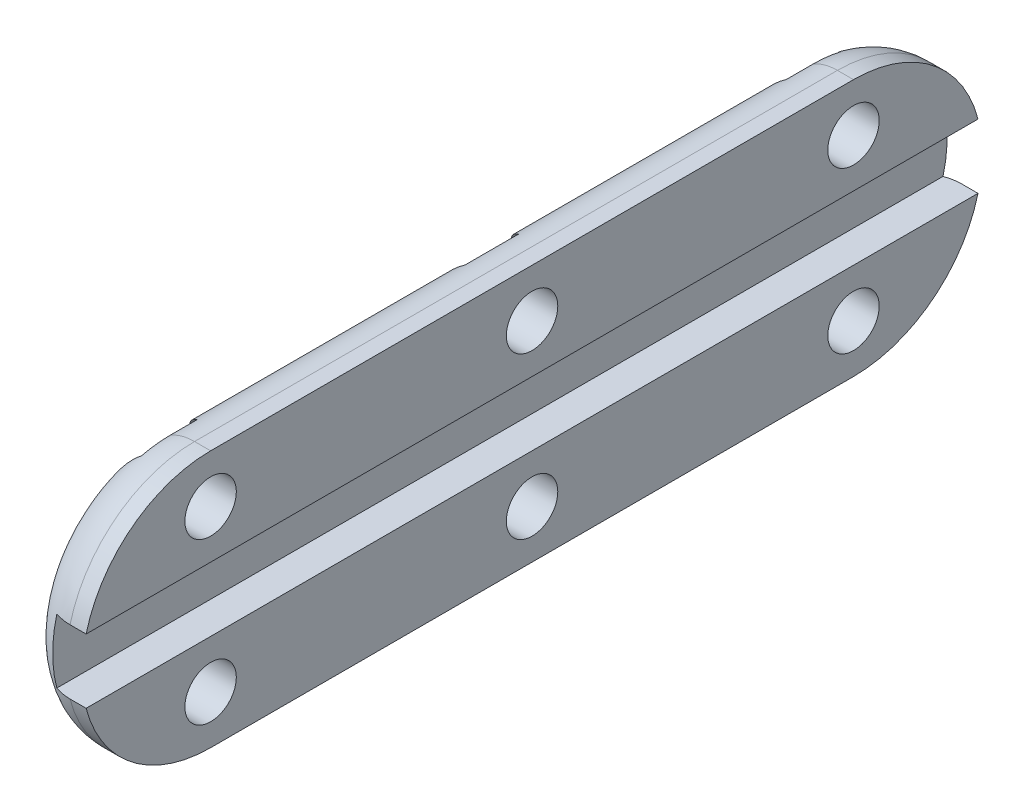
SolidWorks part; units mm, degrees
ref_plane "Front Plane" through (0, 0, 0) normal (0, 0, 1) x (1, 0, 0)
ref_plane "Top Plane" through (0, 0, 0) normal (0, 1, 0) x (1, 0, 0)
ref_plane "Right Plane" through (0, 0, 0) normal (1, 0, 0) x (0, 0, -1)
sketch "Sketch1" plane through (0, 0, 0) normal (1, 0, 0) x (0, 0, -1)
  line L0 (0, 8) -> (0, -8) construction
  line L1 (0, -8) -> (40, -8)
  line L2 (40, -8) -> (40, 8) construction
  line L3 (40, 8) -> (0, 8)
  arc A0 (0, 8) -> (0, -8) centre (0, 0) ccw
  arc A1 (40, 8) -> (40, -8) centre (40, 0) cw
  point P3 (0, 0)
  dimension "D1" = 16
  dimension "D2" = 40
extrude "Boss-Extrude1" add sketch "Sketch1" against normal blind 4
sketch "Sketch2" plane through (0, 0, 0) normal (0, 0, 1) x (1, 0, 0)
  line L0 (0, -8) -> (0, 8) construction
  line L1 (0, 2) -> (-2, 2)
  line L2 (0, 2) -> (0, -2)
  line L3 (0, -2) -> (-2, -2)
  line L4 (-2, 2) -> (-2, -2)
  point P6 (0, 0)
  dimension "D1" = 4
  dimension "D2" = 2
extrude "Cut-Extrude1" cut sketch "Sketch2" against normal through all both and the other way through all
sketch "Sketch3" plane through (0, 0, 0) normal (1, 0, 0) x (0, 0, -1)
  line L0 (0, 5) -> (40, 5) construction
  line L1 (0, 8) -> (0, -8) construction
  line L2 (40, -8) -> (40, 8) construction
  line L3 (0, -5) -> (40, -5) construction
  line L4 (40, 8) -> (0, 8) construction
  line L6 (0, -8) -> (40, -8) construction
  circle A0 centre (0, 5) radius 1.6
  circle A1 centre (40, 5) radius 1.6
  circle A2 centre (40, -5) radius 1.6
  circle A3 centre (0, -5) radius 1.6
  circle A4 centre (20, 5) radius 1.6
  circle A5 centre (20, -5) radius 1.6
  dimension "D3" = 3.2
  dimension "D1" = 3
  dimension "D2" = 3
extrude "Cut-Extrude2" cut sketch "Sketch3" against normal up to next
fillet "Fillet1" radius 3 4 edges at (-4, -8, -20) (-4, 0, 8) (-4, 8, -20) (-4, 0, -48)
sketch "Sketch4" plane through (-4, 0, 0) normal (-1, 0, 0) x (0, 0, 1)
  line L0 (0, 8) -> (0, -8) construction
  line L1 (-36.8246, 5) -> (-38.4123, 7.75)
  line L2 (-38.4123, 7.75) -> (-41.5877, 7.75)
  line L3 (-41.5877, 7.75) -> (-43.1754, 5)
  line L4 (-43.1754, 5) -> (-41.5877, 2.25)
  line L5 (-41.5877, 2.25) -> (-38.4123, 2.25)
  line L6 (-38.4123, 2.25) -> (-36.8246, 5)
  line L7 (-3.1754, 5) -> (-1.5877, 2.25)
  line L8 (-1.5877, 2.25) -> (1.5877, 2.25)
  line L9 (1.5877, 2.25) -> (3.1754, 5)
  line L10 (3.1754, 5) -> (1.5877, 7.75)
  line L11 (1.5877, 7.75) -> (-1.5877, 7.75)
  line L12 (-1.5877, 7.75) -> (-3.1754, 5)
  line L13 (0, 5) -> (-40, 5) construction
  line L14 (-3.1754, -5) -> (-1.5877, -7.75)
  line L15 (-1.5877, -7.75) -> (1.5877, -7.75)
  line L16 (1.5877, -7.75) -> (3.1754, -5)
  line L17 (3.1754, -5) -> (1.5877, -2.25)
  line L18 (1.5877, -2.25) -> (-1.5877, -2.25)
  line L19 (-1.5877, -2.25) -> (-3.1754, -5)
  line L20 (-36.8246, -5) -> (-38.4123, -2.25)
  line L21 (-38.4123, -2.25) -> (-41.5877, -2.25)
  line L22 (-41.5877, -2.25) -> (-43.1754, -5)
  line L23 (-43.1754, -5) -> (-41.5877, -7.75)
  line L24 (-41.5877, -7.75) -> (-38.4123, -7.75)
  line L25 (-38.4123, -7.75) -> (-36.8246, -5)
  line L26 (0, -5) -> (-40, -5) construction
  line L28 (-16.8246, 5) -> (-18.4123, 7.75)
  line L29 (-18.4123, 7.75) -> (-21.5877, 7.75)
  line L30 (-21.5877, 7.75) -> (-23.1754, 5)
  line L31 (-23.1754, 5) -> (-21.5877, 2.25)
  line L32 (-21.5877, 2.25) -> (-18.4123, 2.25)
  line L33 (-18.4123, 2.25) -> (-16.8246, 5)
  line L34 (-16.8246, -5) -> (-18.4123, -2.25)
  line L35 (-18.4123, -2.25) -> (-21.5877, -2.25)
  line L36 (-21.5877, -2.25) -> (-23.1754, -5)
  line L37 (-23.1754, -5) -> (-21.5877, -7.75)
  line L38 (-21.5877, -7.75) -> (-18.4123, -7.75)
  line L39 (-18.4123, -7.75) -> (-16.8246, -5)
  circle A0 centre (-40, 5) radius 2.75 construction
  circle A1 centre (0, 5) radius 2.75 construction
  circle A2 centre (0, -5) radius 2.75 construction
  circle A3 centre (-40, -5) radius 2.75 construction
  circle A4 centre (-20, 5) radius 2.75 construction
  circle A5 centre (-20, -5) radius 2.75 construction
  dimension "D1" = 5.5
  dimension "D2" = 5.5
  dimension "D3" = 5.5
  dimension "D4" = 5.5
extrude "Cut-Extrude3" cut sketch "Sketch4" against normal blind 1.5
